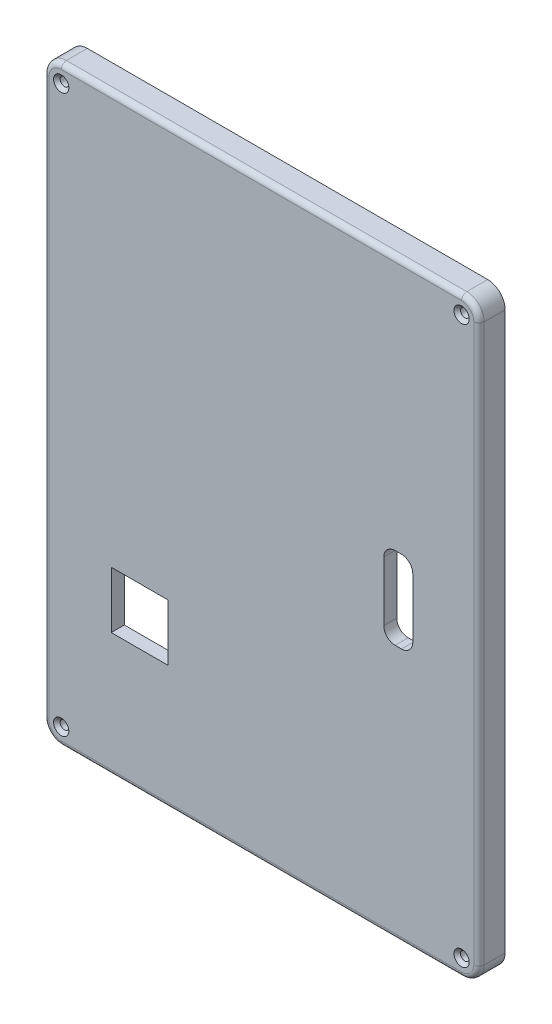
SolidWorks part; units mm, degrees
ref_plane "前视基准面" through (0, 0, 0) normal (0, 0, 1) x (1, 0, 0)
ref_plane "上视基准面" through (0, 0, 0) normal (0, 1, 0) x (1, 0, 0)
ref_plane "右视基准面" through (0, 0, 0) normal (1, 0, 0) x (0, 0, -1)
other "Configuration Table"
sketch "草图1" plane through (0, 0, 0) normal (0, 0, 1) x (1, 0, 0)
  line L1 (-25, -34) -> (25, -34)
  line L2 (-25, -34) -> (-25, 34)
  line L3 (-25, 34) -> (25, 34)
  line L4 (25, -34) -> (25, 34)
  line L5 (-25, -34) -> (25, 34) construction
  line L6 (-25, 34) -> (25, -34) construction
  line L7 (-21.5, -30.5) -> (21.5, -30.5)
  line L8 (-21.5, -30.5) -> (-21.5, 30.5)
  line L9 (-21.5, 30.5) -> (21.5, 30.5)
  line L10 (21.5, -30.5) -> (21.5, 30.5)
  line L11 (-21.5, -30.5) -> (21.5, 30.5) construction
  line L12 (-21.5, 30.5) -> (21.5, -30.5) construction
  line L13 (-23, -32) -> (23, -32) construction
  line L14 (-23, -32) -> (-23, 32) construction
  line L15 (-23, 32) -> (23, 32) construction
  line L16 (23, -32) -> (23, 32) construction
  line L17 (-23, -32) -> (23, 32) construction
  line L18 (-23, 32) -> (23, -32) construction
  circle A0 centre (-23, 32) radius 0.5
  circle A1 centre (23, 32) radius 0.5
  circle A2 centre (23, -32) radius 0.5
  circle A3 centre (-23, -32) radius 0.5
  point P0 (0, 0)
  point P6 (0, 0)
  point P12 (0, 0)
extrude "凸台-拉伸1" add sketch "草图1" along normal blind 3 contours L1 L4 L3 L2 A3 A2 A1 A0 L10 L7 L8 L9 | A2 | A3 | A0 | A1 | L8 L7 L10 L9 region at (-24.156, 0, 0) region at (-23, 32, 0) region at (23, 32, 0) region at (23, -32, 0) region at (-23, -32, 0)
fillet "圆角1" radius 2 4 edges at (-25, -34, 1.5) (25, -34, 1.5) (25, 34, 1.5) (-25, 34, 1.5)
extrude "切除-拉伸1" cut sketch "草图1<5>" along normal through all contours A1 | A0 | A3 | A2 region at (-23, 32, 0) region at (23, 32, 0)
sketch "草图1<5>" plane through (0, 0, 0) normal (0, 0, 1) x (1, 0, 0) same geometry as "草图1"
extrude "切除-拉伸2" cut sketch "草图1<6>" along normal blind 1.5 contours L7 L10 L9 L8 region at (0, 0, 0)
sketch "草图1<6>" plane through (0, 0, 0) normal (0, 0, 1) x (1, 0, 0) same geometry as "草图1"
chamfer "倒角1" distance 0.376 angle 45 4 edges at (-22.5, -32, 3) (-22.5, 32, 3) (23.5, 32, 3) (23.5, -32, 3)
sketch "草图5" plane through (0, 0, 3) normal (0, 0, 1) x (1, 0, 0)
  line L0 (0, 0) -> (15.724, 0) construction
  line L2 (15.3577, -4.7142) -> (16.0903, -4.7142)
  line L3 (14.0577, -3.4142) -> (14.0577, 3.4142)
  line L4 (15.3577, 4.7142) -> (16.0903, 4.7142)
  line L5 (17.3903, -3.4142) -> (17.3903, 3.4142)
  line L6 (14.0577, -4.7142) -> (17.3903, 4.7142) construction
  line L7 (14.0577, 4.7142) -> (17.3903, -4.7142) construction
  arc A0 (16.0903, -4.7142) -> (17.3903, -3.4142) centre (16.0903, -3.4142) ccw
  arc A1 (15.3577, -4.7142) -> (14.0577, -3.4142) centre (15.3577, -3.4142) cw
  arc A2 (16.0903, 4.7142) -> (17.3903, 3.4142) centre (16.0903, 3.4142) cw
  arc A3 (14.0577, 3.4142) -> (15.3577, 4.7142) centre (15.3577, 3.4142) cw
  dimension "D1" = 1.3
extrude "切除-拉伸3" cut sketch "草图5" against normal through all
sketch "草图6" plane through (0, 0, 0) normal (0, 0, 1) x (1, 0, 0)
  line L0 (0, 0) -> (0, 15) construction
  line L2 (-7, 11.5) -> (7, 11.5)
  line L3 (-7, 11.5) -> (-7, 18.5)
  line L4 (-7, 18.5) -> (7, 18.5)
  line L5 (7, 11.5) -> (7, 18.5)
  line L6 (-7, 11.5) -> (7, 18.5) construction
  line L7 (-7, 18.5) -> (7, 11.5) construction
  line L8 (0, 0) -> (-14, 0) construction
  line L9 (0, 0) -> (0, -16.5) construction
  line L10 (0, -16.5) -> (-14, -16.5) construction
  line L11 (-14, 0) -> (-14, -16.5) construction
  line L12 (-17.25, -19.75) -> (-10.75, -19.75)
  line L13 (-17.25, -19.75) -> (-17.25, -13.25)
  line L14 (-17.25, -13.25) -> (-10.75, -13.25)
  line L15 (-10.75, -19.75) -> (-10.75, -13.25)
  line L16 (-17.25, -19.75) -> (-10.75, -13.25) construction
  line L17 (-17.25, -13.25) -> (-10.75, -19.75) construction
extrude "切除-拉伸4" cut sketch "草图6" along normal blind 2 contours L3 L4 L5 L2
extrude "切除-拉伸5" cut sketch "草图6<3>" along normal through all contours L13 L12 L15 L14
sketch "草图6<3>" plane through (0, 0, 0) normal (0, 0, 1) x (1, 0, 0) same geometry as "草图6"
fillet "圆角2" radius 0.6 8 edges at (-24.4142, 33.4142, 3) (0, 34, 3) (24.4142, 33.4142, 3) (25, 0, 3) (24.4142, -33.4142, 3) (0, -34, 3) (-24.4142, -33.4142, 3) (-25, 0, 3)
